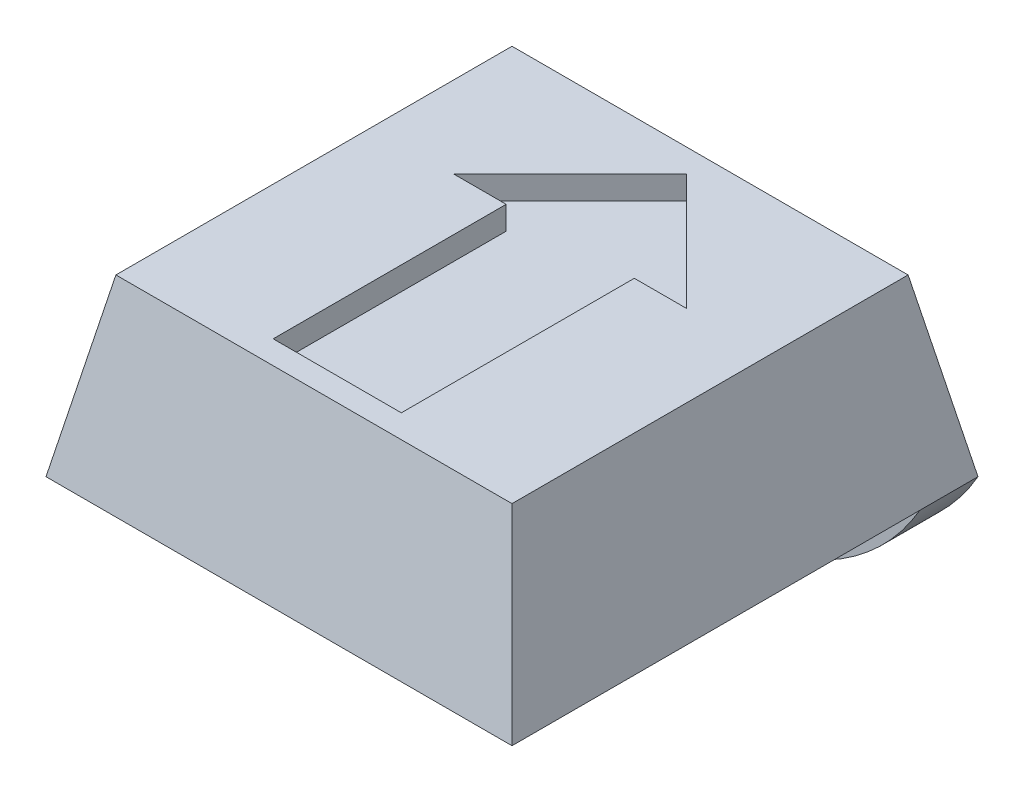
SolidWorks part; units mm, degrees
ref_plane "Front Plane" through (0, 0, 0) normal (0, 0, 1) x (1, 0, 0)
ref_plane "Top Plane" through (0, 0, 0) normal (0, 1, 0) x (1, 0, 0)
ref_plane "Right Plane" through (0, 0, 0) normal (1, 0, 0) x (0, 0, -1)
sketch "Sketch1" plane through (0, 0, 0) normal (0, 1, 0) x (1, 0, 0)
  line L1 (0, 0) -> (8, 0)
  line L2 (0, 0) -> (0, 8)
  line L3 (0, 8) -> (8, 8)
  line L4 (8, 0) -> (8, 8)
  dimension "D1" = 8
  dimension "D2" = 8
extrude "Boss-Extrude1" add sketch "Sketch1" along normal blind 3
sketch "Sketch2" plane through (0, 0, 0) normal (0, 0, 1) x (1, 0, 0)
  line L0 (0, 0) -> (0.6, 3)
  line L1 (0, 3) -> (8, 3) construction
  line L2 (0.6, 3) -> (0, 3)
  line L3 (0, 3) -> (0, 0)
  line L4 (8, 0) -> (7.4, 3)
  line L5 (7.4, 3) -> (8, 3)
  line L6 (8, 3) -> (8, 0)
  dimension "D1" = 0.6
  dimension "D2" = 0.6
extrude "Cut-Extrude1" cut sketch "Sketch2" against normal through all both and the other way through all
sketch "Sketch3" plane through (0, 0, 0) normal (1, 0, 0) x (0, 0, -1)
  line L0 (0, 0) -> (0.6, 3)
  line L1 (8, 3) -> (0, 3) construction
  line L2 (0.6, 3) -> (0, 3)
  line L3 (0, 3) -> (0, 0)
  line L4 (8, 3) -> (7.4, 3)
  line L5 (7.4, 3) -> (8, 0)
  line L6 (8, 3) -> (8, 0)
  dimension "D1" = 0.6
  dimension "D2" = 0.6
extrude "Cut-Extrude2" cut sketch "Sketch3" along normal blind 11
sketch "Sketch4" plane through (0, 0, 0) normal (0, -1, 0) x (1, 0, 0)
  line L0 (8, 0) -> (8, -8) construction
  line L3 (0, 0) -> (8, 0) construction
  circle A0 centre (4, -3.75) radius 1.75
  dimension "D1" = 3.5
  dimension "D2" = 4
  dimension "D3" = 3.75
extrude "Cut-Extrude3" cut sketch "Sketch4" against normal blind 0.4
sketch "Sketch5" plane through (0, 0, 0) normal (0, -1, 0) x (1, 0, 0)
  line L0 (8, 0) -> (8, -8) construction
  line L1 (0, -8) -> (8, -8)
  line L2 (0, -8) -> (0, -7)
  line L3 (0, -7) -> (8, -7)
  line L4 (8, -8) -> (8, -7)
  dimension "D1" = 1
extrude "Boss-Extrude2" add sketch "Sketch5" along normal blind 2
fillet "Fillet1" radius 4 2 edges at (8, -2, -7.5) (0, -2, -7.5)
sketch "Sketch6" plane through (0, 3, 0) normal (0, 1, 0) x (1, 0, 0)
  line L0 (2.9, 5) -> (2, 5)
  line L1 (2.9, 5) -> (5.1, 5)
  line L2 (2.9, 5) -> (2.9, 1)
  line L3 (2.9, 1) -> (5.1, 1)
  line L4 (5.1, 5) -> (5.1, 1)
  line L5 (2, 5) -> (4, 7)
  line L6 (4, 7) -> (6, 5)
  line L7 (6, 5) -> (5.1, 5)
  line L8 (0.6, 7.4) -> (0.6, 0.6) construction
  line L9 (7.4, 7.4) -> (7.4, 0.6) construction
  line L10 (7.4, 0.6) -> (0.6, 0.6) construction
  line L11 (7.4, 7.4) -> (0.6, 7.4) construction
  point P15 (4, 7.4)
  dimension "D1" = 2.3
  dimension "D2" = 2.3
  dimension "D3" = 0.4
  dimension "D4" = 0.4
  dimension "D5" = 1.4
  dimension "D6" = 1.4
  dimension "D7" = 0
  dimension "D8" = 4
extrude "Cut-Extrude4" cut sketch "Sketch6" against normal blind 0.4 contours L4 L1 L2 L3 | L7 L6 L5 L0 L1 region at (4, 3, -5.6667) region at (4, 3, -3)
